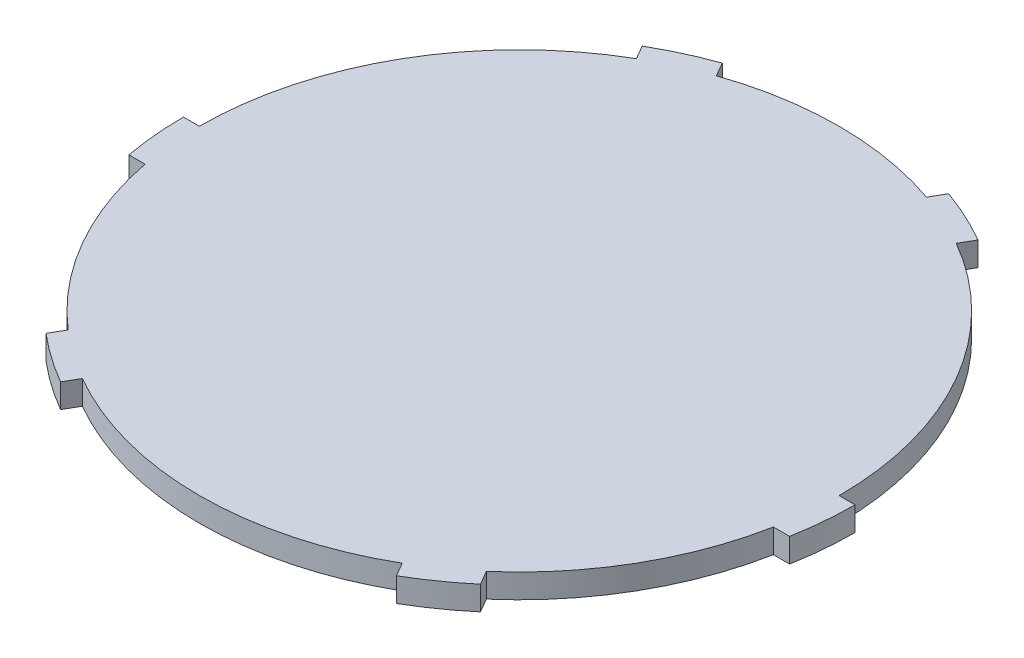
SolidWorks part; units mm, degrees
ref_plane "Front Plane" through (0, 0, 0) normal (0, 0, 1) x (1, 0, 0)
ref_plane "Top Plane" through (0, 0, 0) normal (0, 1, 0) x (1, 0, 0)
ref_plane "Right Plane" through (0, 0, 0) normal (1, 0, 0) x (0, 0, -1)
sketch "Sketch1" plane through (0, 0, 0) normal (0, 1, 0) x (1, 0, 0)
  line L0 (13.3111, 23.0555) -> (13.9742, 24.204) construction
  line L1 (-13.9742, -24.204) -> (-13.3111, -23.0555) construction
  line L2 (-17.4043, -20.1452) -> (-18.0789, -21.3135) construction
  line L3 (13.9742, -24.204) -> (13.3111, -23.0555) construction
  line L4 (17.4043, -20.1452) -> (18.0789, -21.3135) construction
  line L5 (27.4975, -5) -> (26.1484, -5) construction
  line L6 (27.9484, 0) -> (26.6221, 0) construction
  line L7 (9.4186, 26.3135) -> (8.7441, 25.1452) construction
  line L8 (6, 25.9372) -> (6, 21.5) construction
  line L9 (6, 21.5) -> (7.8417, 21.5) construction
  line L10 (12, 17.3417) -> (12, -16.5) construction
  line L11 (12, 17.3417) -> (12, -16.5)
  line L12 (6, 21.5) -> (7.8417, 21.5)
  line L13 (6, 25.9372) -> (6, 21.5)
  line L14 (9.4186, 26.3135) -> (8.7441, 25.1452)
  line L15 (13.3111, 23.0555) -> (13.9742, 24.204)
  line L16 (27.9484, 0) -> (26.6221, 0)
  line L17 (27.4975, -5) -> (26.1484, -5)
  line L18 (17.4043, -20.1452) -> (18.0789, -21.3135)
  line L19 (13.9742, -24.204) -> (13.3111, -23.0555)
  line L20 (-17.4043, -20.1452) -> (-18.0789, -21.3135)
  line L21 (-13.9742, -24.204) -> (-13.3111, -23.0555)
  line L22 (12, -16.5) -> (-12, -16.5) construction
  line L23 (12, -16.5) -> (-12, -16.5)
  line L24 (0, 0) -> (0, -16.5) construction
  line L25 (-13.3111, 23.0555) -> (-13.9742, 24.204) construction
  line L26 (-9.4186, 26.3135) -> (-8.7441, 25.1452) construction
  line L27 (-6, 25.9372) -> (-6, 21.5) construction
  line L28 (-7.6227, 21.5) -> (-6, 21.5) construction
  line L29 (-12, 20.8183) -> (-12, 21.5) construction
  line L30 (-12, 16.5) -> (-12, 17.5017) construction
  line L31 (-20, 15.5) -> (-13, 15.5) construction
  line L32 (-12, -16.5) -> (-12, 0.5) construction
  line L33 (-17, 5.5) -> (-20, 5.5) construction
  line L34 (-20, 5.5) -> (-20, 15.5) construction
  line L35 (-13.3111, 23.0555) -> (-13.9742, 24.204)
  line L36 (-9.4186, 26.3135) -> (-8.7441, 25.1452)
  line L37 (-6, 25.9372) -> (-6, 21.5)
  line L38 (-7.6227, 21.5) -> (-6, 21.5)
  line L39 (-12, 20.8183) -> (-12, 21.5)
  line L40 (-12, 16.5) -> (-12, 17.5017)
  line L41 (-20, 15.5) -> (-13, 15.5)
  line L42 (-12, -16.5) -> (-12, 0.5)
  line L43 (-17, 5.5) -> (-20, 5.5)
  line L44 (-20, 5.5) -> (-20, 15.5)
  line L45 (-26.1484, -5) -> (-27.4975, -5) construction
  line L46 (-26.6221, 0) -> (-27.9484, 0) construction
  line L47 (-26.6221, 0) -> (-27.9484, 0)
  line L48 (-26.1484, -5) -> (-27.4975, -5)
  arc A1 (-13.3111, -23.0555) -> (13.3111, -23.0555) centre (0, 0) ccw construction
  arc A2 (-18.0789, -21.3135) -> (-13.9742, -24.204) centre (0, 0) ccw construction
  arc A3 (-26.1484, -5) -> (-17.4043, -20.1452) centre (0, 0) ccw construction
  arc A4 (13.9742, -24.204) -> (18.0789, -21.3135) centre (0, 0) ccw construction
  arc A5 (17.4043, -20.1452) -> (26.1484, -5) centre (0, 0) ccw construction
  arc A6 (27.4975, -5) -> (27.9484, 0) centre (0, 0) ccw construction
  arc A7 (26.6221, 0) -> (13.3111, 23.0555) centre (0, 0) ccw construction
  arc A8 (13.9742, 24.204) -> (9.4186, 26.3135) centre (0, 0) ccw construction
  arc A9 (8.7441, 25.1452) -> (6, 25.9372) centre (0, 0) ccw construction
  arc A10 (12, 17.3417) -> (12.3619, 19.8996) centre (9.5, 19) ccw construction
  arc A11 (10.3996, 21.8619) -> (7.8417, 21.5) centre (9.5, 19) ccw construction
  arc A12 (10.3996, 21.8619) -> (12, 21.5) centre (13.3982, 31.4018) ccw construction
  arc A13 (12, 21.5) -> (12.3619, 19.8996) centre (21.9018, 22.8982) ccw construction
  arc A14 (12, 17.3417) -> (12.3619, 19.8996) centre (9.5, 19) ccw
  arc A15 (12, 21.5) -> (12.3619, 19.8996) centre (21.9018, 22.8982) ccw
  arc A16 (10.3996, 21.8619) -> (12, 21.5) centre (13.3982, 31.4018) ccw
  arc A17 (10.3996, 21.8619) -> (7.8417, 21.5) centre (9.5, 19) ccw
  arc A18 (8.7441, 25.1452) -> (6, 25.9372) centre (0, 0) ccw
  arc A19 (13.9742, 24.204) -> (9.4186, 26.3135) centre (0, 0) ccw
  arc A20 (26.6221, 0) -> (13.3111, 23.0555) centre (0, 0) ccw
  arc A21 (27.4975, -5) -> (27.9484, 0) centre (0, 0) ccw
  arc A22 (17.4043, -20.1452) -> (26.1484, -5) centre (0, 0) ccw
  arc A23 (13.9742, -24.204) -> (18.0789, -21.3135) centre (0, 0) ccw
  arc A24 (-26.1484, -5) -> (-17.4043, -20.1452) centre (0, 0) ccw
  arc A25 (-18.0789, -21.3135) -> (-13.9742, -24.204) centre (0, 0) ccw
  arc A26 (-13.3111, -23.0555) -> (13.3111, -23.0555) centre (0, 0) ccw
  arc A27 (-13.3111, 23.0555) -> (-26.6221, 0) centre (0, 0) ccw construction
  arc A28 (-9.4186, 26.3135) -> (-13.9742, 24.204) centre (0, 0) ccw construction
  arc A29 (-6, 25.9372) -> (-8.7441, 25.1452) centre (0, 0) ccw construction
  arc A30 (-7.6227, 21.5) -> (-10.6213, 21.9425) centre (-9.5, 19.16) ccw construction
  arc A31 (-12, 21.5) -> (-10.6213, 21.9425) centre (-14.3589, 31.2178) ccw construction
  arc A32 (-12, 20.8183) -> (-12, 17.5017) centre (-9.5, 19.16) ccw construction
  arc A33 (-13, 15.5) -> (-12, 16.5) centre (-13, 16.5) ccw construction
  arc A34 (-12, 0.5) -> (-17, 5.5) centre (-17, 0.5) ccw construction
  arc A35 (-13.3111, 23.0555) -> (-26.6221, 0) centre (0, 0) ccw
  arc A36 (-9.4186, 26.3135) -> (-13.9742, 24.204) centre (0, 0) ccw
  arc A37 (-6, 25.9372) -> (-8.7441, 25.1452) centre (0, 0) ccw
  arc A38 (-7.6227, 21.5) -> (-10.6213, 21.9425) centre (-9.5, 19.16) ccw
  arc A39 (-12, 21.5) -> (-10.6213, 21.9425) centre (-14.3589, 31.2178) ccw
  arc A40 (-12, 20.8183) -> (-12, 17.5017) centre (-9.5, 19.16) ccw
  arc A41 (-13, 15.5) -> (-12, 16.5) centre (-13, 16.5) ccw
  arc A42 (-12, 0.5) -> (-17, 5.5) centre (-17, 0.5) ccw
  arc A43 (-27.9484, 0) -> (-27.4975, -5) centre (0, 0) ccw construction
  arc A44 (-27.9484, 0) -> (-27.4975, -5) centre (0, 0) ccw
  circle A45 centre (0, 0) radius 26.6221
extrude "Boss-Extrude1" add sketch "Sketch1" along normal blind 2 contours L13 A45 L37 L38 A38 A39 L39 A40 L40 A41 L41 L44 L43 A42 L42 L23 L11 A14 A15 A16 A17 L12 | A26 A45 A22 A20 A18 L13 L12 A17 A16 A15 A14 L11 L23 L42 A42 L43 L44 L41 A41 L40 A40 L39 A39 A38 L38 L37 A37 A35 A24 | A45 L15 A19 L14 | A45 L36 A36 L35 | A45 L17 A21 L16 | A45 L19 A23 L18 | A45 L20 A25 L21 | A45 L47 A44 L48 region at (13.2112, 0, -18.4749) region at (-1.2783, 0, -4.3933) region at (11.3943, 0, -24.7497) region at (-11.3943, 0, -24.7497) region at (27.131, 0, 2.5071) region at (-27.131, 0, 2.5071) region at (15.7367, 0, 22.2426) region at (-15.7367, 0, 22.2426)
sketch "Sketch2" plane through (0, 0, 0) normal (0, -1, 0) x (1, 0, 0)
  line L0 (-6, -25.9372) -> (6, -25.9372) construction
  line L1 (-5.8, -25.7372) -> (5.8, -25.7372)
  line L2 (5.8, -21.3) -> (5.8, -25.7372)
  line L3 (7.9031, -21.3) -> (5.8, -21.3)
  line L4 (11.8, 16.3) -> (11.8, -17.4031)
  line L5 (-11.8, 16.3) -> (11.8, 16.3)
  line L6 (-11.8, -0.5) -> (-11.8, 16.3)
  line L7 (-19.8, -5.7) -> (-17, -5.7)
  line L8 (-19.8, -15.3) -> (-19.8, -5.7)
  line L9 (-13, -15.3) -> (-19.8, -15.3)
  line L10 (-11.8, -17.5631) -> (-11.8, -16.5)
  line L11 (-11.8, -21.344) -> (-11.8, -20.7568)
  line L12 (-5.8, -21.3) -> (-7.6944, -21.3)
  line L13 (-5.8, -25.7372) -> (-5.8, -21.3)
  line L24 (-12, -0.5) -> (-12, 16.5)
  line L25 (-12, 16.5) -> (12, 16.5)
  line L26 (12, 16.5) -> (12, -17.3417)
  line L27 (7.8417, -21.5) -> (6, -21.5)
  line L28 (6, -21.5) -> (6, -25.9372)
  line L29 (8.7441, -25.1452) -> (9.4186, -26.3135)
  line L30 (13.9742, -24.204) -> (13.3111, -23.0555)
  line L31 (26.6221, 0) -> (27.9484, 0)
  line L32 (27.4975, 5) -> (26.1484, 5)
  line L33 (17.4043, 20.1452) -> (18.0789, 21.3135)
  line L34 (13.9742, 24.204) -> (13.3111, 23.0555)
  line L35 (-13.3111, 23.0555) -> (-13.9742, 24.204)
  line L36 (-18.0789, 21.3135) -> (-17.4043, 20.1452)
  line L37 (-26.1484, 5) -> (-27.4975, 5)
  line L38 (-27.9484, 0) -> (-26.6221, 0)
  line L39 (-13.3111, -23.0555) -> (-13.9742, -24.204)
  line L40 (-9.4186, -26.3135) -> (-8.7441, -25.1452)
  line L41 (-6, -25.9372) -> (-6, -21.5)
  line L42 (-6, -21.5) -> (-7.6227, -21.5)
  line L43 (-12, -21.5) -> (-12, -20.8183)
  line L44 (-12, -17.5017) -> (-12, -16.5)
  line L45 (-13, -15.5) -> (-20, -15.5)
  line L46 (-20, -15.5) -> (-20, -5.5)
  line L47 (-20, -5.5) -> (-17, -5.5)
  line L48 (-12, -0.5) -> (-12, 16.5) construction
  line L49 (-12, 16.5) -> (12, 16.5) construction
  line L50 (12, 16.5) -> (12, -17.3417) construction
  line L51 (7.8417, -21.5) -> (6, -21.5) construction
  line L52 (6, -21.5) -> (6, -25.9372) construction
  line L65 (-6, -25.9372) -> (-6, -21.5) construction
  line L66 (-6, -21.5) -> (-7.6227, -21.5) construction
  line L67 (-12, -21.5) -> (-12, -20.8183) construction
  line L68 (-12, -17.5017) -> (-12, -16.5) construction
  line L69 (-13, -15.5) -> (-20, -15.5) construction
  line L70 (-20, -15.5) -> (-20, -5.5) construction
  line L71 (-20, -5.5) -> (-17, -5.5) construction
  arc A0 (7.9031, -21.3) -> (10.3396, -21.6711) centre (9.5, -19) ccw
  arc A1 (11.824, -21.324) -> (10.3396, -21.6711) centre (13.3982, -31.4018) ccw
  arc A3 (12.1711, -19.8396) -> (11.824, -21.324) centre (21.9018, -22.8982) ccw
  arc A4 (12.1711, -19.8396) -> (11.8, -17.4031) centre (9.5, -19) ccw
  arc A5 (-17, -5.7) -> (-11.8, -0.5) centre (-17, -0.5) ccw
  arc A6 (-11.8, -16.5) -> (-13, -15.3) centre (-13, -16.5) ccw
  arc A7 (-11.8, -17.5631) -> (-11.8, -20.7568) centre (-9.5, -19.16) ccw
  arc A8 (-10.5465, -21.757) -> (-11.8, -21.344) centre (-14.3589, -31.2178) ccw
  arc A9 (-10.5465, -21.757) -> (-7.6944, -21.3) centre (-9.5, -19.16) ccw
  arc A24 (12.3619, -19.8996) -> (12, -17.3417) centre (9.5, -19) ccw
  arc A25 (12.3619, -19.8996) -> (12, -21.5) centre (21.9018, -22.8982) ccw
  arc A26 (12, -21.5) -> (10.3996, -21.8619) centre (13.3982, -31.4018) ccw
  arc A27 (7.8417, -21.5) -> (10.3996, -21.8619) centre (9.5, -19) ccw
  arc A28 (6, -25.9372) -> (8.7441, -25.1452) centre (0, 0) ccw
  arc A29 (9.4186, -26.3135) -> (13.9742, -24.204) centre (0, 0) ccw
  arc A30 (13.3111, -23.0555) -> (26.6221, 0) centre (0, 0) ccw
  arc A31 (27.9484, 0) -> (27.4975, 5) centre (0, 0) ccw
  arc A32 (26.1484, 5) -> (17.4043, 20.1452) centre (0, 0) ccw
  arc A33 (18.0789, 21.3135) -> (13.9742, 24.204) centre (0, 0) ccw
  arc A34 (13.3111, 23.0555) -> (-13.3111, 23.0555) centre (0, 0) ccw
  arc A35 (-13.9742, 24.204) -> (-18.0789, 21.3135) centre (0, 0) ccw
  arc A36 (-17.4043, 20.1452) -> (-26.1484, 5) centre (0, 0) ccw
  arc A37 (-27.4975, 5) -> (-27.9484, 0) centre (0, 0) ccw
  arc A38 (-26.6221, 0) -> (-13.3111, -23.0555) centre (0, 0) ccw
  arc A39 (-13.9742, -24.204) -> (-9.4186, -26.3135) centre (0, 0) ccw
  arc A40 (-8.7441, -25.1452) -> (-6, -25.9372) centre (0, 0) ccw
  arc A41 (-10.6213, -21.9425) -> (-7.6227, -21.5) centre (-9.5, -19.16) ccw
  arc A42 (-10.6213, -21.9425) -> (-12, -21.5) centre (-14.3589, -31.2178) ccw
  arc A43 (-12, -17.5017) -> (-12, -20.8183) centre (-9.5, -19.16) ccw
  arc A44 (-12, -16.5) -> (-13, -15.5) centre (-13, -16.5) ccw
  arc A45 (-17, -5.5) -> (-12, -0.5) centre (-17, -0.5) ccw
  arc A46 (12.3619, -19.8996) -> (12, -17.3417) centre (9.5, -19) ccw construction
  arc A47 (12.3619, -19.8996) -> (12, -21.5) centre (21.9018, -22.8982) ccw construction
  arc A48 (12, -21.5) -> (10.3996, -21.8619) centre (13.3982, -31.4018) ccw construction
  arc A49 (7.8417, -21.5) -> (10.3996, -21.8619) centre (9.5, -19) ccw construction
  arc A63 (-10.6213, -21.9425) -> (-7.6227, -21.5) centre (-9.5, -19.16) ccw construction
  arc A64 (-10.6213, -21.9425) -> (-12, -21.5) centre (-14.3589, -31.2178) ccw construction
  arc A65 (-12, -17.5017) -> (-12, -20.8183) centre (-9.5, -19.16) ccw construction
  arc A66 (-12, -16.5) -> (-13, -15.5) centre (-13, -16.5) ccw construction
  arc A67 (-17, -5.5) -> (-12, -0.5) centre (-17, -0.5) ccw construction
  dimension "D1" = 0.2
  dimension "D2" = 0
extrude "Boss-Extrude2" add sketch "Sketch2" along normal blind 2
sketch "Sketch4" plane through (0, -2, 0) normal (0, -1, 0) x (1, 0, 0)
  line L26 (-4.3, -19.8) -> (-4.3, -24.2372)
  line L27 (-4.3, -24.2372) -> (4.3, -24.2372)
  line L28 (4.3, -24.2372) -> (4.3, -19.8)
  line L29 (4.3, -19.8) -> (8.4753, -19.8)
  line L30 (10.3, -17.9753) -> (10.3, 14.8)
  line L31 (10.3, 14.8) -> (-10.3, 14.8)
  line L32 (-10.3, 14.8) -> (-10.3, -0.5)
  line L33 (-17, -7.2) -> (-18.3, -7.2)
  line L34 (-18.3, -7.2) -> (-18.3, -13.8)
  line L35 (-18.3, -13.8) -> (-13, -13.8)
  line L36 (-10.3, -16.5) -> (-10.3, -18.1353)
  line L37 (-10.3, -20.1847) -> (-10.3, -20.2444)
  line L38 (-8.3685, -19.8) -> (-4.3, -19.8)
  line L39 (-4.3, -19.8) -> (-4.3, -24.2372)
  line L40 (-4.3, -24.2372) -> (4.3, -24.2372)
  line L41 (4.3, -24.2372) -> (4.3, -19.8)
  line L42 (4.3, -19.8) -> (8.4753, -19.8)
  line L43 (10.3, -17.9753) -> (10.3, 14.8)
  line L44 (10.3, 14.8) -> (-10.3, 14.8)
  line L45 (-10.3, 14.8) -> (-10.3, -0.5)
  line L46 (-17, -7.2) -> (-18.3, -7.2)
  line L47 (-18.3, -7.2) -> (-18.3, -13.8)
  line L48 (-18.3, -13.8) -> (-13, -13.8)
  line L49 (-10.3, -16.5) -> (-10.3, -18.1353)
  line L50 (-10.3, -20.1847) -> (-10.3, -20.2444)
  line L51 (-8.3685, -19.8) -> (-4.3, -19.8)
  arc A18 (8.4753, -19.8) -> (9.8898, -20.2402) centre (9.5, -19) ccw
  arc A19 (10.553, -20.053) -> (9.8898, -20.2402) centre (13.3982, -31.4018) ccw
  arc A20 (10.7402, -19.3898) -> (10.553, -20.053) centre (21.9018, -22.8982) ccw
  arc A21 (10.7402, -19.3898) -> (10.3, -17.9753) centre (9.5, -19) ccw
  arc A22 (-17, -7.2) -> (-10.3, -0.5) centre (-17, -0.5) ccw
  arc A23 (-10.3, -16.5) -> (-13, -13.8) centre (-13, -16.5) ccw
  arc A24 (-10.3, -18.1353) -> (-10.3, -20.1847) centre (-9.5, -19.16) ccw
  arc A25 (-9.9859, -20.3658) -> (-10.3, -20.2444) centre (-14.3589, -31.2178) ccw
  arc A26 (-9.9859, -20.3658) -> (-8.3685, -19.8) centre (-9.5, -19.16) ccw
  arc A27 (8.4753, -19.8) -> (9.8898, -20.2402) centre (9.5, -19) ccw
  arc A28 (10.553, -20.053) -> (9.8898, -20.2402) centre (13.3982, -31.4018) ccw
  arc A29 (10.7402, -19.3898) -> (10.553, -20.053) centre (21.9018, -22.8982) ccw
  arc A30 (10.7402, -19.3898) -> (10.3, -17.9753) centre (9.5, -19) ccw
  arc A31 (-17, -7.2) -> (-10.3, -0.5) centre (-17, -0.5) ccw
  arc A32 (-10.3, -16.5) -> (-13, -13.8) centre (-13, -16.5) ccw
  arc A33 (-10.3, -18.1353) -> (-10.3, -20.1847) centre (-9.5, -19.16) ccw
  arc A34 (-9.9859, -20.3658) -> (-10.3, -20.2444) centre (-14.3589, -31.2178) ccw
  arc A35 (-9.9859, -20.3658) -> (-8.3685, -19.8) centre (-9.5, -19.16) ccw
  dimension "D1" = 1.5
extrude "Cut-Extrude1" cut sketch "Sketch4" against normal blind 2
fillet "Fillet1" radius 2 2 edges at (11.824, -1, -21.324) (-11.8, -1, -21.344)
fillet "Fillet2" radius 1 6 edges at (11.8, -1, 16.3) (-11.8, -1, 16.3) (-19.8, -1, -5.7) (-19.8, -1, -15.3) (5.8, -1, -25.7372) (-5.8, -1, -25.7372)
